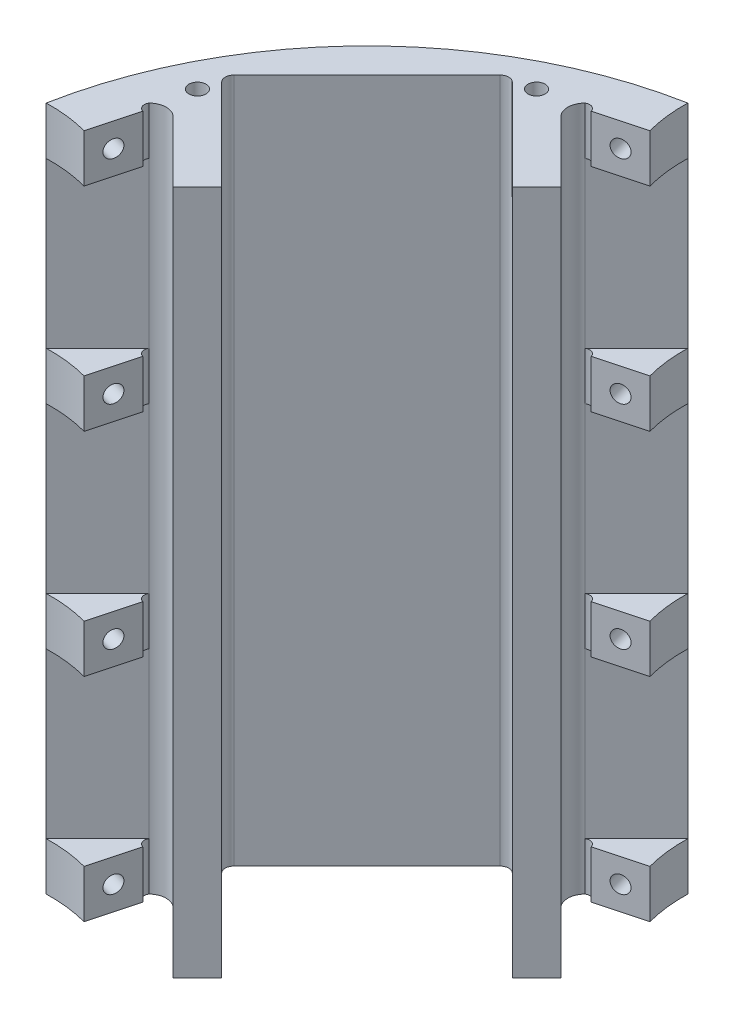
SolidWorks part; units mm, degrees
material "6061-T6 (SS)"
ref_plane "Front Plane" through (0, 0, 0) normal (0, 0, 1) x (1, 0, 0)
ref_plane "Top Plane" through (0, 0, 0) normal (0, 1, 0) x (1, 0, 0)
ref_plane "Right Plane" through (0, 0, 0) normal (1, 0, 0) x (0, 0, -1)
sketch "Constraints" plane through (0, 0, 0) normal (0, 1, 0) x (1, 0, 0)
  line L0 (0, 152.4) -> (0, -152.4) construction
  line L1 (-152.4, 0) -> (152.4, 0) construction
  circle A0 centre (0, 0) radius 152.4 construction
  circle A1 centre (0, 0) radius 149.225 construction
  circle A2 centre (0, 0) radius 12.7 construction
  circle A3 centre (0, 76.454) radius 12.7 construction
  circle A4 centre (76.454, 0) radius 12.7 construction
  circle A5 centre (0, -76.454) radius 12.7 construction
  circle A6 centre (-76.454, 0) radius 12.7 construction
  point P20 (0, 0)
  dimension "D1" = 25.4
  dimension "D4" = 304.8
  dimension "D3" = 76.454
  dimension "D2" = 3.175
  dimension "D6" = 76.454
  dimension "D7" = 76.454
  dimension "D5" = 4
sketch "Base" plane through (0, 0, 0) normal (0, 1, 0) x (1, 0, 0)
  line L0 (0, 76.454) -> (-76.454, 0) construction
  line L5 (21.8789, -21.8789) -> (-16.3481, 16.3481) construction
  line L9 (-27.6819, 146.635) -> (-51.2374, 123.0795)
  line L10 (-123.0795, 69.1979) -> (-87.1584, 33.2769)
  line L11 (-69.1979, 123.0795) -> (-123.0795, 69.1979)
  line L12 (-69.1979, 123.0795) -> (-33.2769, 87.1584)
  line L13 (-33.2769, 87.1584) -> (-24.2966, 96.1387)
  line L14 (-24.2966, 96.1387) -> (-51.2374, 123.0795)
  line L15 (-146.635, 27.6819) -> (-123.0795, 51.2374)
  line L16 (-96.1387, 24.2966) -> (-123.0795, 51.2374)
  line L17 (-87.1584, 33.2769) -> (-96.1387, 24.2966)
  line L18 (-19.5371, 78.1962) -> (-81.4004, 16.3329) construction
  arc A2 (-146.635, 27.6819) -> (-27.6819, 146.635) centre (0, 0) cw
  circle A3 centre (0, 0) radius 149.225 construction
  point P18 (-96.1387, 96.1387)
  dimension "D2" = 12.7
  dimension "D4" = 38.1
  dimension "D5" = 50.8
  dimension "D6" = 16.0528
  dimension "D3" = 76.2
  dimension "D1" = 68.619
extrude "Cradle" add sketch "Base" along normal blind 254 contours L9 L14 L13 L12 L11 L10 L17 L16 L15 A2
ref_plane "Mirror Plane 1" through (0, 127, 0) normal (0, 1, 0) x (1, 0, 0)
sketch "Sketch1" plane through (0, 254, 0) normal (0, 1, 0) x (1, 0, 0)
  line L0 (-51.2374, 123.0795) -> (-69.1979, 123.0795) construction
  line L1 (-69.1979, 123.0795) -> (-33.2769, 87.1584) construction
  line L2 (-69.1979, 123.0795) -> (-123.0795, 69.1979) construction
  line L4 (-96.1387, 96.1387) -> (-75.7363, 75.7363) construction
  circle A0 centre (-60.2177, 123.0795) radius 3.175
  circle A1 centre (-123.0795, 60.2177) radius 3.175
  point P2 (-60.2177, 123.0795)
  point P11 (-96.1387, 96.1387)
  dimension "D1" = 6.35
extrude "Cut-Extrude1" cut sketch "Sketch1" against normal blind 12.7 contours A1 | A0 region at (-123.0795, 254, -60.2177)
mirror "Mirror1" about plane through (0, 127, 0) normal (0, 1, 0) of "Cut-Extrude1"
ref_plane "Mirror Plane 2" through (0, 0, 0) normal (-0.7071, 0, 0.7071) x (0.7071, 0, 0.7071)
fillet "Eigth Inch Fillets" radius 3.175 2 edges at (-123.0795, 127, -69.1979) (-69.1979, 127, -123.0795)
fillet "Quarter Inch Fillets" radius 6.35 2 edges at (-123.0795, 127, -51.2374) (-51.2374, 127, -123.0795)
sketch "Sketch4" plane through (26.9408, 0, -26.9408) normal (-0.7071, 0, 0.7071) x (0.7071, 0, 0.7071)
  line L4 (-85.1607, 103.1875) -> (-85.1607, 150.8125) construction
  line L5 (-132.7857, 254) -> (-132.7857, 0) construction
  line L6 (-132.7857, 254) -> (-85.1607, 254) construction
  circle A0 centre (-108.9732, 127) radius 1.27
  circle A1 centre (-108.9732, 101.6) radius 1.27
  circle A2 centre (-108.9732, 76.2) radius 1.27
  circle A3 centre (-108.9732, 50.8) radius 1.27
  circle A4 centre (-108.9732, 25.4) radius 1.27
  circle A5 centre (-108.9732, 127) radius 1.27
  circle A6 centre (-108.9732, 101.6) radius 1.27
  circle A7 centre (-108.9732, 76.2) radius 1.27
  circle A8 centre (-108.9732, 50.8) radius 1.27
  circle A9 centre (-108.9732, 152.4) radius 1.27
  circle A10 centre (-108.9732, 127) radius 1.27
  circle A11 centre (-108.9732, 101.6) radius 1.27
  circle A12 centre (-108.9732, 76.2) radius 1.27
  circle A13 centre (-108.9732, 177.8) radius 1.27
  circle A14 centre (-108.9732, 152.4) radius 1.27
  circle A15 centre (-108.9732, 127) radius 1.27
  circle A16 centre (-108.9732, 101.6) radius 1.27
  circle A17 centre (-108.9732, 203.2) radius 1.27
  circle A18 centre (-108.9732, 177.8) radius 1.27
  circle A19 centre (-108.9732, 152.4) radius 1.27
  circle A20 centre (-108.9732, 127) radius 1.27
  circle A21 centre (-108.9732, 152.4) radius 1.27
  circle A22 centre (-108.9732, 177.8) radius 1.27
  circle A23 centre (-108.9732, 203.2) radius 1.27
  circle A25 centre (-96.2732, 25.4) radius 1.27
  circle A26 centre (-96.2732, 50.8) radius 1.27
  circle A27 centre (-96.2732, 76.2) radius 1.27
  circle A28 centre (-96.2732, 101.6) radius 1.27
  circle A29 centre (-96.2732, 127) radius 1.27
  circle A30 centre (-96.2732, 152.4) radius 1.27
  circle A31 centre (-96.2732, 177.8) radius 1.27
  circle A32 centre (-96.2732, 203.2) radius 1.27
  circle A33 centre (-96.2732, 228.6) radius 1.27
  circle A34 centre (-108.9732, 25.4) radius 1.27
  circle A35 centre (-108.9732, 50.8) radius 1.27
  circle A36 centre (-108.9732, 76.2) radius 1.27
  circle A37 centre (-108.9732, 101.6) radius 1.27
  circle A38 centre (-108.9732, 127) radius 1.27
  circle A39 centre (-108.9732, 152.4) radius 1.27
  circle A40 centre (-108.9732, 177.8) radius 1.27
  circle A41 centre (-108.9732, 203.2) radius 1.27
  circle A52 centre (-121.6732, 152.4) radius 1.27 [skipped]
  circle A53 centre (-121.6732, 177.8) radius 1.27 [skipped]
  circle A54 centre (-121.6732, 203.2) radius 1.27 [skipped]
  circle A55 centre (-108.9732, 228.6) radius 1.27
  circle A56 centre (-108.9732, 228.6) radius 1.27 [skipped]
  circle A57 centre (-121.6732, 101.6) radius 1.27 [skipped]
  circle A58 centre (-121.6732, 127) radius 1.27 [skipped]
  circle A59 centre (-121.6732, 25.4) radius 1.27 [skipped]
  circle A60 centre (-121.6732, 50.8) radius 1.27 [skipped]
  circle A61 centre (-121.6732, 76.2) radius 1.27 [skipped]
  dimension "D1" = 2.54
  dimension "D9" = 47.625
  dimension "D6" = 11.1125
  dimension "D7" = 23.8125
  dimension "D8" = 25.4
  dimension "D10" = 50.8
  dimension "D2" = 5
  dimension "D3" = 5
extrude "Wire Holes" cut sketch "Sketch4" against normal through all contours A4 | A25 | A3 | A26 | A2 | A27 | A1 | A28 | A0 | A29 | A9 | A30 | A13 | A31 | A17 | A32 | A33 | A55 region at (-50.1149, 127, -103.9964) region at (-50.1149, 101.6, -103.9964) region at (-50.1149, 76.2, -103.9964) region at (-50.1149, 50.8, -103.9964) region at (-50.1149, 25.4, -103.9964) region at (-50.1149, 152.4, -103.9964) region at (-50.1149, 177.8, -103.9964) region at (-50.1149, 203.2, -103.9964) region at (-41.1346, 25.4, -95.0162) region at (-41.1346, 50.8, -95.0162) region at (-41.1346, 76.2, -95.0162) region at (-41.1346, 101.6, -95.0162) region at (-41.1346, 127, -95.0162) region at (-41.1346, 152.4, -95.0162) region at (-41.1346, 177.8, -95.0162) region at (-41.1346, 203.2, -95.0162) region at (-41.1346, 228.6, -95.0162) region at (-50.1149, 228.6, -103.9964)
sketch "Sketch5" plane through (0, 0, 0) normal (0, 1, 0) x (1, 0, 0)
  line L0 (-42.9979, 126.122) -> (-25.8237, 130.7238)
  line L1 (-39.444, 147.2071) -> (-32.87, 122.6726)
  line L3 (-27.6819, 146.635) -> (-46.7473, 127.5696)
  line L4 (0, 152.4) -> (0, -152.4) construction
  line L5 (0, 152.4) -> (0, -152.4) construction
  line L6 (0, 0) -> (-18.9361, 70.6706) construction
  arc A1 (-25.8237, 130.7238) -> (-27.6819, 146.635) centre (27.5232, 145.018) cw
  arc A2 (-42.9979, 126.122) -> (-46.7473, 127.5696) centre (-45.4006, 125.4781) ccw
  circle A3 centre (0, 0) radius 152.4 construction
  point P2 (0, 0)
  point P10 (-34.4108, 128.4229)
  point P12 (-39.444, 147.2071)
  dimension "D1" = 17.78
  dimension "D2" = 15
  dimension "D3" = 25.4
  dimension "D4" = 5.9531
extrude "Boss-Extrude1" add sketch "Sketch5" along normal blind 17.78 contours L0 A1 L3 A2
sketch "Sketch6" plane through (-34.4108, 0, -128.4229) normal (0.2588, 0, 0.9659) x (0.9659, 0, -0.2588)
  line L0 (8.89, 0) -> (-8.89, 17.78) construction
  circle A0 centre (0, 8.89) radius 3.175
  dimension "D1" = 6.35
extrude "Cut-Extrude2" cut sketch "Sketch6" against normal through all contours A0
pattern_linear "LPattern1" count 4 spacing 78.74 along (0, 1, 0) of "Boss-Extrude1", "Cut-Extrude2"
mirror "Mirror2" about plane through (0, 0, 0) normal (-0.7071, 0, 0.7071) of "LPattern1", "Cut-Extrude2", "Boss-Extrude1"
equation "\"Pipe Diameter\"= 1in"
equation "\"D1@Constraints\"=\"Pipe Diameter\""
equation "\"Pipe Radial Distance\"= 3.01in"
equation "\"D3@Constraints\"=\"Pipe Radial Distance\""
equation "\"Rocket Diameter\"= 12in"
equation "\"D4@Constraints\"=\"Rocket Diameter\""
equation "\"Airframe Thickness\"= 0.125in"
equation "\"D2@Constraints\"=\"Airframe Thickness\""
equation "\"D6@Constraints\"=\"Pipe Radial Distance\""
equation "\"D7@Constraints\"=\"Pipe Radial Distance\""
equation "\"Arduino Mega Length\"= 101.52mm"
equation "\"Arduino Mega Width\"= 53.3mm"
equation "\"Interior Height\"= 2in"
equation "\"Wall Thickness\"= 0.5in"
equation "\"Assembly Hole Diameter\"= 0.25in"
equation "\"D2@Base\" = \"Wall Thickness\""
equation "\"D4@Base\" = \"Interior Height\" - \"Wall Thickness\""
equation "\"D5@Base\" = \"Interior Height\""
equation "\"4-40 Standoff Depth\"= 0.1875in"
equation "\"D1@Cradle\"=10in"
equation "\"D1@Sketch1\"=\"Assembly Hole Diameter\""
equation "\"D1@Cut-Extrude1\"=\"Wall Thickness\""
equation "\"D1@Eigth Inch Fillets\" = 0.5 * \"Assembly Hole Diameter\""
equation "\"Wire Hole Diameter\"= 0.1in"
equation "\"D1@Sketch4\"=\"Wire Hole Diameter\""
equation "\"Flange Nut Height\"= 15 / 64in"
equation "\"Flange Nut Diameter\"= 19 / 32in"
equation "\"Assembly Bolt Length\"= 1in"
equation "\"D1@Sketch6\"=\"Assembly Hole Diameter\""
